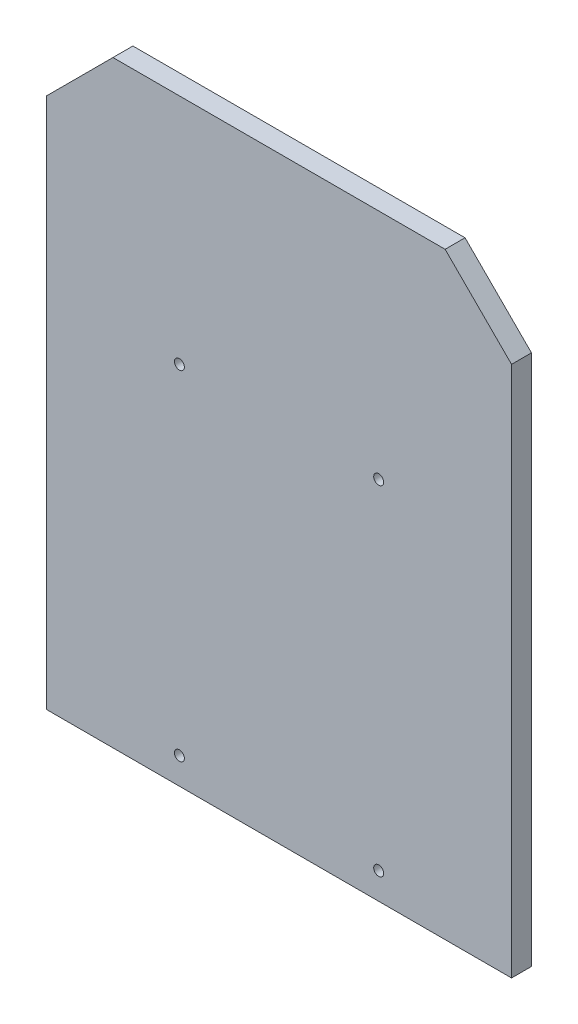
SolidWorks part; units mm, degrees
ref_plane "Alzado" through (0, 0, 0) normal (0, 0, 1) x (1, 0, 0)
ref_plane "Planta" through (0, 0, 0) normal (0, 1, 0) x (1, 0, 0)
ref_plane "Vista lateral" through (0, 0, 0) normal (1, 0, 0) x (0, 0, -1)
sketch "Croquis1" plane through (0, 0, 0) normal (0, 0, 1) x (1, 0, 0)
  line L5 (-30.0455, 36.9284) -> (39.9545, 36.9284)
  line L6 (-30.0455, 36.9284) -> (-30.0455, -53.0716)
  line L7 (-30.0455, -53.0716) -> (39.9545, -53.0716)
  line L8 (39.9545, 36.9284) -> (39.9545, -53.0716)
  dimension "D1" = 70
  dimension "D2" = 90
extrude "Saliente-Extruir1" add sketch "Croquis1" along normal blind 3
sketch "Croquis2" plane through (0, 0, 0) normal (0, 0, -1) x (-1, 0, 0)
  line L0 (-34.9545, -49.5716) -> (-39.9545, -49.5716) construction
  line L1 (-39.9545, -53.0716) -> (-39.9545, 36.9284) construction
  line L2 (25.0455, -49.5716) -> (30.0455, -49.5716) construction
  line L3 (30.0455, 36.9284) -> (30.0455, -53.0716) construction
  line L4 (25.0455, -49.5716) -> (25.0455, -53.0716) construction
  line L5 (30.0455, -53.0716) -> (-39.9545, -53.0716) construction
  line L6 (-34.9545, -49.5716) -> (-34.9545, -53.0716) construction
  line L7 (-34.9545, -6.5716) -> (-34.9545, -49.5716) construction
  circle A0 centre (-34.9545, -49.5716) radius 1
  circle A1 centre (25.0455, -49.5716) radius 1
  circle A2 centre (-34.9545, -6.5716) radius 1
  circle A3 centre (25.0455, -6.5716) radius 1
extrude "Cortar-Extruir1" cut sketch "Croquis2" against normal blind 3
sketch "Croquis3" plane through (0, 0, 0) normal (0, 0, -1) x (-1, 0, 0)
  line L1 (-39.9545, 36.9284) -> (30.0455, 36.9284) construction
  line L3 (-39.9545, -53.0716) -> (-39.9545, 36.9284) construction
  line L5 (-39.9545, 36.9284) -> (30.0455, 36.9284)
  line L6 (-39.9545, -53.0716) -> (-39.9545, 36.9284)
fillet "Chaflán1" radius 10 1 edges at (39.9545, 36.9284, 1.5) type face fillet profile chamfer first side face at (39.9545, -8.0716, 1.5) second side face at (4.9545, 36.9284, 1.5)
fillet "Chaflán2" radius 10 1 edges at (-30.0455, 36.9284, 1.5) type face fillet profile chamfer first side face at (-0.0455, 36.9284, 1.5) second side face at (-30.0455, -8.0716, 1.5)
sketch "Croquis4" plane through (0, 0, 3) normal (0, 0, 1) x (1, 0, 0)
  line L1 (-28.5234, -2.4605) -> (37.6758, -2.4605)
  line L2 (-28.5234, -2.4605) -> (-28.5234, -53.0716)
  line L3 (-28.5234, -53.0716) -> (37.6758, -53.0716)
  line L4 (37.6758, -2.4605) -> (37.6758, -53.0716)
  line L5 (-28.5234, -2.4605) -> (37.6758, -53.0716) construction
  line L6 (-28.5234, -53.0716) -> (37.6758, -2.4605) construction
  point P4 (4.5762, -27.766)
extrude "Saliente-Extruir2" add sketch "Croquis4" against normal blind 3
sketch "Croquis5" plane through (0, 0, 3) normal (0, 0, 1) x (1, 0, 0)
  line L0 (-30.0455, -53.0716) -> (39.9545, -53.0716) construction
  line L1 (-30.0455, 26.9284) -> (-30.0455, -53.0716) construction
  line L2 (39.9545, -53.0716) -> (39.9545, 36.9284) construction
  circle A0 centre (-10.0455, 1.9284) radius 0.75
  circle A1 centre (19.9545, 1.9284) radius 0.75
  circle A5 centre (-10.0455, -49.0716) radius 0.75
  circle A6 centre (19.9545, -49.0716) radius 0.75
  dimension "D1" = 1.5
  dimension "D2" = 55
  dimension "D6" = 20
  dimension "D7" = 20
  dimension "D8" = 20
  dimension "D9" = 51
  dimension "D10" = 4
  dimension "D3" = 20
  dimension "D4" = 4
  dimension "D5" = 55
extrude "Cortar-Extruir2" cut sketch "Croquis5" against normal through all
